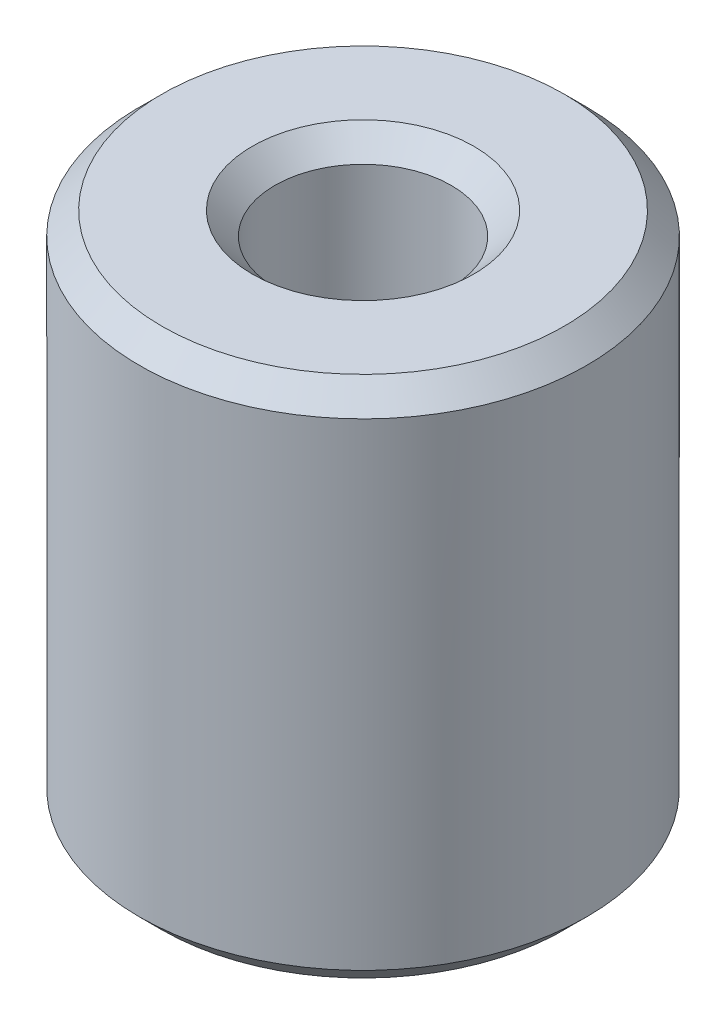
SolidWorks part; units mm, degrees
ref_plane "Front Plane" through (0, 0, 0) normal (0, 0, 1) x (1, 0, 0)
ref_plane "Top Plane" through (0, 0, 0) normal (0, 1, 0) x (1, 0, 0)
ref_plane "Right Plane" through (0, 0, 0) normal (1, 0, 0) x (0, 0, -1)
sketch "Sketch1" plane through (0, 0, 0) normal (0, 1, 0) x (1, 0, 0)
  circle A0 centre (0, 0) radius 37.5
  dimension "SLEEVE_OD" = 75
extrude "Boss-Extrude1" add sketch "Sketch1" along normal blind 87.6345
sketch "Sketch2" plane through (0, 0, 0) normal (0, 1, 0) x (1, 0, 0)
  circle A0 centre (0, 0) radius 14.7852
  dimension "BORE_D" = 29.5704
extrude "Cut-Extrude1" cut sketch "Sketch2" along normal through all
chamfer "Chamfer1" distance 3.7851 angle 45 4 edges at (0, 87.6345, 14.7852) (0, 0, 14.7852) (0, 0, 37.5) (0, 87.6345, 37.5)
